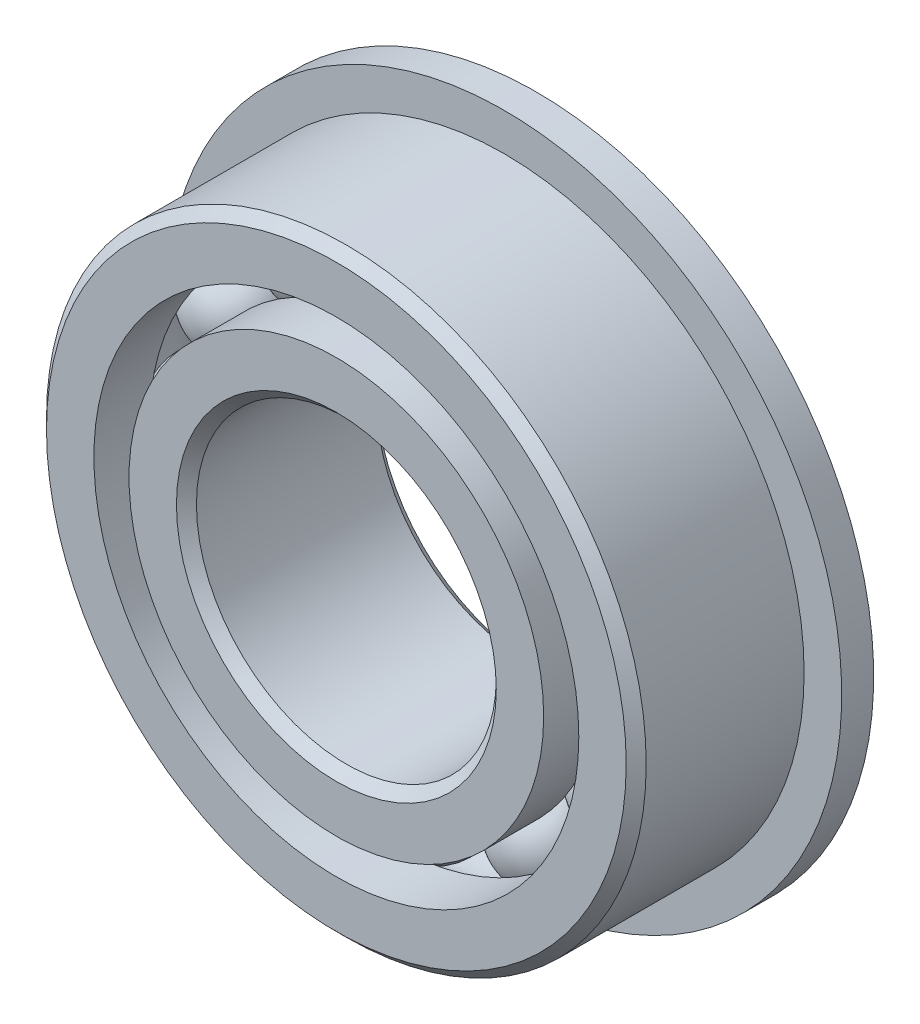
SolidWorks part; units mm, degrees
ref_plane "Front Plane" through (0, 0, 0) normal (0, 0, 1) x (1, 0, 0)
ref_plane "Top Plane" through (0, 0, 0) normal (0, 1, 0) x (1, 0, 0)
ref_plane "Right Plane" through (0, 0, 0) normal (1, 0, 0) x (0, 0, -1)
sketch "Sketch1" plane through (0, 0, 0) normal (1, 0, 0) x (0, 0, -1)
  line L0 (-1.5875, 0) -> (1.5875, 0) construction
  line L1 (0, 4.7625) -> (0, -4.7625) construction
  line L2 (1.4288, 4.7625) -> (-1.4288, 4.7625)
  line L3 (-1.4288, 4.7625) -> (-1.5875, 4.6037)
  line L4 (-1.5875, 4.6037) -> (-1.5875, 3.851)
  line L5 (-1.5875, 3.851) -> (-0.7056, 3.851)
  line L6 (1.5875, 3.851) -> (0.7056, 3.851)
  line L7 (1.5875, 4.6037) -> (1.5875, 3.851)
  line L8 (1.4288, 4.7625) -> (1.5875, 4.6037)
  line L9 (0, 4.7625) -> (0, 3.5719) construction
  line L10 (0, 3.5719) -> (0, 2.3813) construction
  arc A0 (-0.7056, 3.851) -> (0.7056, 3.851) centre (0, 3.5719) cw
  point P14 (0, 2.3813)
  dimension "D3" = 1.4111
  dimension "D1" = 45
  dimension "Width" = 3.175
  dimension "OD" = 9.525
  dimension "D2" = 0.1588
  dimension "Shaft Dia" = 4.7625
  dimension "D4" = 0.2791
revolve "Revolve1" add sketch "Sketch1" angle 360 about L0
sketch "Sketch3" plane through (0, 0, 0) normal (1, 0, 0) x (0, 0, -1)
  line L0 (-1.5875, 3.2928) -> (-0.7056, 3.2928)
  line L1 (0, 4.7625) -> (0, -4.7625) construction
  line L2 (-1.5875, 4.6037) -> (-1.5875, 3.851) construction
  line L3 (-1.5875, 3.2928) -> (-1.5875, 2.54)
  line L4 (-1.4288, 4.7625) -> (-1.5875, 4.6037) construction
  line L5 (-1.5875, 2.54) -> (-1.4288, 2.3812)
  line L6 (-1.4288, 2.3812) -> (1.4288, 2.3812)
  line L7 (1.4288, 4.7625) -> (1.4288, -4.7625) construction
  line L8 (1.4288, 2.3812) -> (1.5875, 2.54)
  line L9 (1.5875, -4.6037) -> (1.5875, 4.6037) construction
  line L10 (1.5875, 2.54) -> (1.5875, 3.2928)
  line L11 (1.5875, 3.2928) -> (0.7056, 3.2928)
  line L13 (1.4288, 4.7625) -> (1.5875, 4.6037) construction
  arc A0 (0.7056, 3.851) -> (-0.7056, 3.851) centre (0, 3.5719) ccw construction
  arc A1 (0.7056, 3.2928) -> (-0.7056, 3.2928) centre (0, 3.5719) cw
revolve "Revolve3" add sketch "Sketch3" angle 360 about L0
sketch "Sketch4" plane through (0, 0, 0) normal (1, 0, 0) x (0, 0, -1)
  line L0 (-0.7588, 3.5719) -> (0.7588, 3.5719)
  arc A2 (-0.7588, 3.5719) -> (0.7588, 3.5719) centre (0, 3.5719) cw
  arc A3 (0.7056, 3.851) -> (-0.7056, 3.851) centre (0, 3.5719) ccw construction
revolve "Revolve4" add sketch "Sketch4" angle 360 about L0
ref_axis "Axis1" through (0, 0, -1.5875) along (0, 0, 1)
pattern_circular "CirPattern1" count 12 every 30 about axis through (0, 0, -1.5875) along (0, 0, 1) of bodies 104
sketch "Sketch5" plane through (0, 0, 0) normal (1, 0, 0) x (0, 0, -1)
  line L0 (-1.5875, 3.851) -> (-0.7056, 3.851) construction
  line L1 (-1.5081, 3.851) -> (-0.7588, 3.851)
  line L2 (-1.5081, 3.851) -> (-1.5081, 3.2928)
  line L3 (-1.5081, 3.2928) -> (-0.7588, 3.2928)
  line L4 (-0.7588, 3.851) -> (-0.7588, 3.2928)
  line L5 (-1.5875, 3.2928) -> (-0.7056, 3.2928) construction
  line L6 (1.5875, 3.851) -> (0.7056, 3.851) construction
  line L7 (1.5081, 3.851) -> (0.7588, 3.851)
  line L8 (1.5081, 3.851) -> (1.5081, 3.2928)
  line L9 (1.5081, 3.2928) -> (0.7588, 3.2928)
  line L10 (0.7588, 3.851) -> (0.7588, 3.2928)
  line L11 (1.5875, 3.2928) -> (0.7056, 3.2928) construction
  line L12 (-1.4288, 4.7625) -> (-1.5875, 4.6037) construction
  point P18 (-1.5081, 4.6831)
revolve "Revolve5" [suppressed] add sketch "Sketch5" angle 360 about L0
sketch "Sketch6" plane through (0, 0, 0) normal (1, 0, 0) x (0, 0, -1)
  line L0 (1.5875, 0) -> (-1.5875, 0) construction
  line L1 (1.5875, 3.851) -> (1.0795, 3.851)
  line L2 (1.5875, 3.851) -> (1.5875, 5.3594)
  line L3 (1.5875, 5.3594) -> (1.0795, 5.3594)
  line L4 (1.0795, 3.851) -> (1.0795, 5.3594)
  dimension "Th" = 0.508
  dimension "Flange OD" = 10.7188
revolve "Revolve6" add sketch "Sketch6" angle 360 about L0
equation "\"D2@Sketch1\" = \"Width@Sketch1\"*.05"
equation "\"D3@Sketch1\" = \"Width@Sketch1\"/2.25"
equation "\"D4@Sketch1\" = (((\"OD@Sketch1\"-\"Width@Sketch1\")/2)/3.25)/3.5"
equation "\"D2@CirPattern1\" = 360/\"Balls@CirPattern1\""
